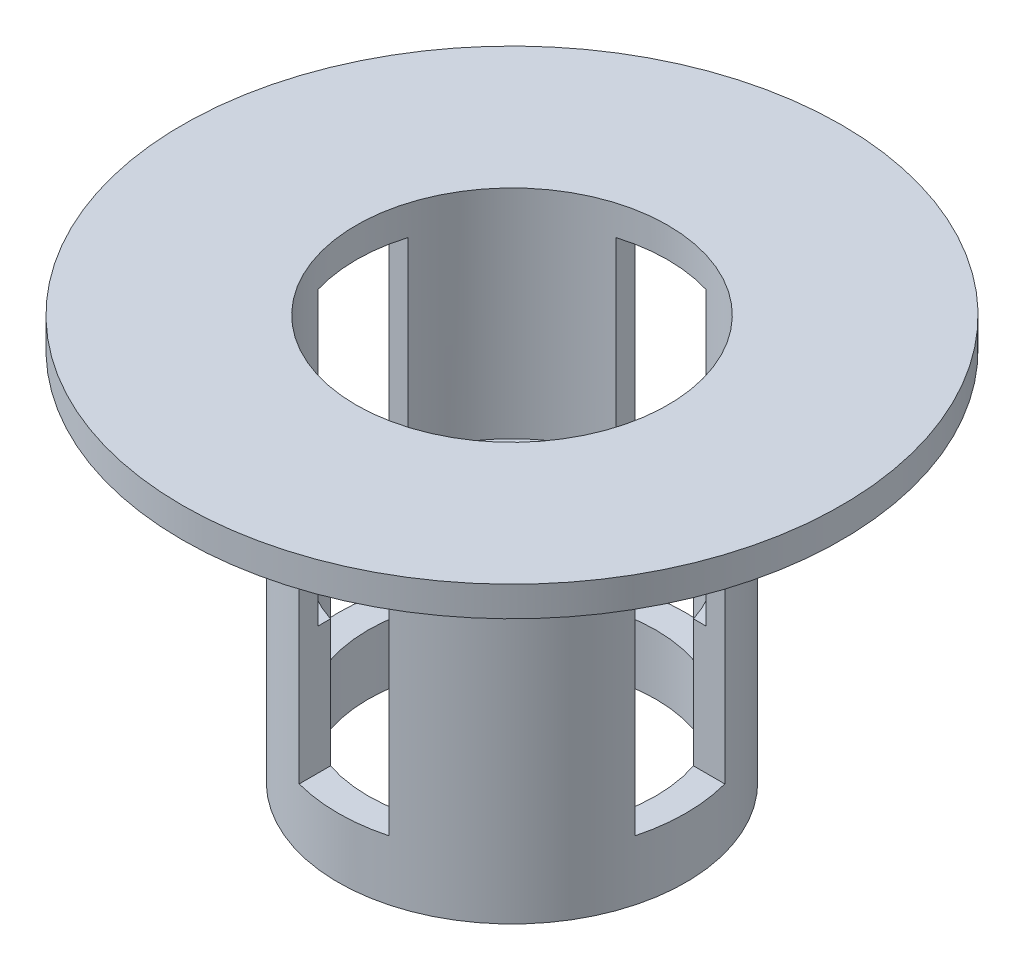
SolidWorks part; units mm, degrees
ref_plane "Front Plane" through (0, 0, 0) normal (0, 0, 1) x (1, 0, 0)
ref_plane "Top Plane" through (0, 0, 0) normal (0, 1, 0) x (1, 0, 0)
ref_plane "Right Plane" through (0, 0, 0) normal (1, 0, 0) x (0, 0, -1)
sketch "Sketch1" plane through (0, 0, 0) normal (0, 1, 0) x (1, 0, 0)
  circle A0 centre (0, 0) radius 6.604
  circle A1 centre (0, 0) radius 13.97
  dimension "D1" = 13.208
  dimension "D2" = 27.94
extrude "Stabilizer" add sketch "Sketch1" along normal blind 1.27
sketch "Sketch2" plane through (0, 0, 0) normal (0, -1, 0) x (-1, 0, 0)
  circle A0 centre (0, 0) radius 6.604
  circle A1 centre (0, 0) radius 7.366
  circle A2 centre (0, 0) radius 6.604 construction
  dimension "D1" = 14.732
extrude "Large End" add sketch "Sketch2" along normal blind 7.9375 contours A1 | A0
sketch "Sketch3" plane through (0, -7.9375, 0) normal (0, -1, 0) x (-1, 0, 0)
  circle A0 centre (0, 0) radius 6.096
  circle A1 centre (0, 0) radius 7.366
  circle A2 centre (0, 0) radius 7.366 construction
  dimension "D1" = 12.192
extrude "Small End" add sketch "Sketch3" along normal blind 7.9375
sketch "Sketch4" plane through (0, -15.875, 0) normal (0, -1, 0) x (-1, 0, 0)
  circle A0 centre (0, 0) radius 7.366 construction
  point P0 (0, -7.366)
ref_plane "Plane1" through (0, -15.875, 7.366) normal (0, 0, 1) x (1, 0, 0)
sketch "Sketch5" plane through (0, -15.875, 7.366) normal (0, 0, 1) x (1, 0, 0)
  line L1 (1.905, 2.54) -> (-1.905, 2.54)
  line L2 (1.905, 2.54) -> (1.905, 15.875)
  line L3 (1.905, 15.875) -> (-1.905, 15.875)
  line L4 (-1.905, 2.54) -> (-1.905, 15.875)
  line L5 (-7.366, 0) -> (7.366, 0) construction
  line L6 (-7.366, 15.875) -> (7.366, 15.875) construction
  dimension "D1" = 3.81
  dimension "D2" = 2.54
extrude "Cut-Extrude1" cut sketch "Sketch5" against normal through all
sketch "Sketch6" plane through (0, -15.875, 0) normal (0, -1, 0) x (-1, 0, 0)
  circle A0 centre (0, 0) radius 7.366 construction
  point P0 (-7.366, 0)
ref_plane "Plane2" through (7.366, -15.875, 0) normal (1, 0, 0) x (0, 0, -1)
sketch "Sketch7" plane through (7.366, -15.875, 0) normal (1, 0, 0) x (0, 0, -1)
  line L0 (-7.366, 0) -> (7.366, 0) construction
  line L1 (1.905, 2.54) -> (-1.905, 2.54)
  line L2 (1.905, 2.54) -> (1.905, 15.875)
  line L3 (1.905, 15.875) -> (-1.905, 15.875)
  line L4 (-1.905, 2.54) -> (-1.905, 15.875)
  line L5 (-7.1154, 15.875) -> (7.1154, 15.875) construction
  line L6 (0, 2.54) -> (0, 0) construction
  dimension "D1" = 3.81
  dimension "D2" = 2.54
extrude "Cut-Extrude2" cut sketch "Sketch7" against normal through all contours L2 L3 L4 L1
